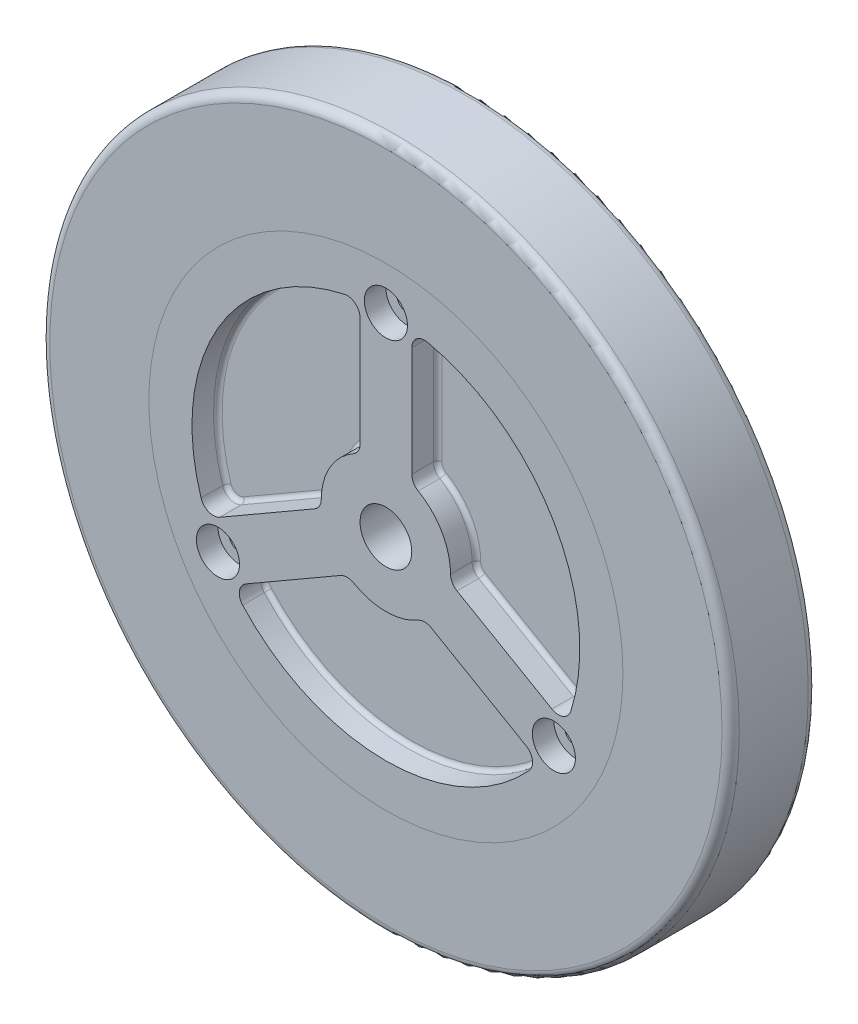
SolidWorks part; units mm, degrees
material "PVC 僵硬"
ref_plane "前视基准面" through (0, 0, 0) normal (0, 0, 1) x (1, 0, 0)
ref_plane "上视基准面" through (0, 0, 0) normal (0, 1, 0) x (1, 0, 0)
ref_plane "右视基准面" through (0, 0, 0) normal (1, 0, 0) x (0, 0, -1)
sketch "草图1" plane through (0, 0, 0) normal (0, 0, 1) x (1, 0, 0)
  circle A0 centre (0, 0) radius 55
  dimension "D1" = 110
extrude "凸台-拉伸1" add sketch "草图1" along normal blind 20
sketch "草图2" plane through (0, 0, 20) normal (0, 0, 1) x (1, 0, 0)
  circle A0 centre (0, 0) radius 2.65
  dimension "D1" = 5.3
extrude "切除-拉伸1" cut sketch "草图2" against normal through all
sketch "草图11" plane through (0, 0, 20) normal (0, 0, 1) x (1, 0, 0)
  circle A0 centre (0, 0) radius 6
  dimension "D1" = 12
extrude "切除-拉伸6" cut sketch "草图11" against normal blind 15
sketch "草图3" plane through (0, 0, 20) normal (0, 0, 1) x (1, 0, 0)
  line L0 (-78.699, 0) -> (94.1302, 0) construction
  line L1 (0, 68.1544) -> (0, -71.9264) construction
  circle A0 centre (0, 45) radius 2.5
  circle A4 centre (38.9711, -22.5) radius 2.5
  circle A5 centre (-38.9711, -22.5) radius 2.5
  circle A6 centre (0, 0) radius 45 construction
  dimension "D1" = 5
  dimension "D2" = 45
  dimension "D3" = 3
extrude "切除-拉伸2" cut sketch "草图3" against normal through all contours A4 | A5 | A0
sketch "草图5" plane through (0, 0, 20) normal (0, 0, 1) x (1, 0, 0)
  circle A0 centre (0, 45) radius 2.5 construction
  circle A2 centre (0, 45) radius 5
  dimension "D1" = 10
extrude "切除-拉伸3" cut sketch "草图5" against normal blind 5
ref_axis "基准轴1" through (0, 0, 0) along (0, 0, 1)
pattern_circular "阵列(圆周)1" count 3 over 360 about axis through (0, 0, 0) along (0, 0, 1) of "切除-拉伸3"
sketch "草图6" plane through (0, 0, 0) normal (0, 0, 1) x (1, 0, 0)
  circle A0 centre (0, 30) radius 2
  circle A1 centre (25.9808, -15) radius 2
  circle A2 centre (-25.9808, -15) radius 2
  dimension "D1" = 4
  dimension "D2" = 30
  dimension "D3" = 3
extrude "切除-拉伸4" cut sketch "草图6" along normal blind 10
sketch "草图7" plane through (0, 0, 0) normal (0, 0, 1) x (1, 0, 0)
  circle A0 centre (0, 0) radius 55 construction
  circle A1 centre (0, 0) radius 55
  circle A2 centre (0, 0) radius 80
  dimension "D1" = 160
extrude "凸台-拉伸2" add sketch "草图7" along normal up to surface (20 mm away) separate body up to face at (-41.4711, -18.1699, 20)
fillet "圆角1" radius 2 2 edges at (80, 0, 0) (80, 0, 20)
ref_plane "基准面1" through (0, 0, 10) normal (0, 0, 1) x (1, 0, 0)
sketch "草图9" plane through (0, 0, 20) normal (0, 0, 1) x (1, 0, 0)
  line L0 (-6, 41.0244) -> (-6, 15.5885)
  line L1 (0, 0) -> (0, 66.1158) construction
  line L2 (6, 41.0244) -> (6, 15.5885)
  line L3 (38.5282, -15.316) -> (16.5, -2.5981)
  line L4 (32.5282, -25.7083) -> (10.5, -12.9904)
  line L5 (-32.5282, -25.7083) -> (-10.5, -12.9904)
  line L6 (-38.5282, -15.316) -> (-16.5, -2.5981)
  arc A0 (-33.2445, -30.3283) -> (33.2445, -30.3283) centre (0, 0) ccw
  arc A1 (-7.5, -12.9904) -> (7.5, -12.9904) centre (0, 0) ccw
  arc A2 (15, 0) -> (7.5, 12.9904) centre (0, 0) ccw
  arc A3 (42.8873, -13.6264) -> (9.6429, 43.9547) centre (0, 0) ccw
  arc A4 (-9.6429, 43.9547) -> (-42.8873, -13.6264) centre (0, 0) ccw
  arc A5 (-7.5, 12.9904) -> (-15, 0) centre (0, 0) ccw
  arc A6 (-10.5, -12.9904) -> (-7.5, -12.9904) centre (-9, -15.5885) cw
  arc A7 (10.5, -12.9904) -> (7.5, -12.9904) centre (9, -15.5885) ccw
  arc A8 (6, 15.5885) -> (7.5, 12.9904) centre (9, 15.5885) ccw
  arc A9 (-6, 15.5885) -> (-7.5, 12.9904) centre (-9, 15.5885) cw
  arc A10 (-16.5, -2.5981) -> (-15, 0) centre (-18, 0) ccw
  arc A11 (-38.5282, -15.316) -> (-42.8873, -13.6264) centre (-40.0282, -12.718) cw
  arc A12 (-32.5282, -25.7083) -> (-33.2445, -30.3283) centre (-31.0282, -28.3064) ccw
  arc A13 (32.5282, -25.7083) -> (33.2445, -30.3283) centre (31.0282, -28.3064) cw
  arc A14 (38.5282, -15.316) -> (42.8873, -13.6264) centre (40.0282, -12.718) ccw
  arc A15 (6, 41.0244) -> (9.6429, 43.9547) centre (9, 41.0244) cw
  arc A16 (-6, 41.0244) -> (-9.6429, 43.9547) centre (-9, 41.0244) ccw
  arc A17 (15, 0) -> (16.5, -2.5981) centre (18, 0) ccw
  point P22 (6, 13.7477)
  point P25 (-6, 13.7477)
  point P38 (6, 44.5982)
  point P41 (-6, 44.5982)
  dimension "D1" = 30
  dimension "D4" = 3
  dimension "D5" = 3
  dimension "D2" = 6
  dimension "D3" = 3
extrude "切除-拉伸5" cut sketch "草图9" against normal blind 6
mirror "镜向1" about plane through (0, 0, 10) normal (0, 0, 1) of "切除-拉伸5"
fillet "圆角2" radius 1 48 edges at (0, -15, 14) (9, -12.5885, 14) (21.5141, -19.3494, 14) (33.9927, -27.8468, 14) (0, -45, 14) (-33.9927, -27.8468, 14) (-21.5141, -19.3494, 14) (-9, -12.5885, 14) (6, 28.3064, 14) (7.1197, 43.362, 14) (38.9711, 22.5, 14) (41.1124, -15.5152, 14) (27.5141, -8.9571, 14) (15.4019, -1.5, 14) (12.9904, 7.5, 14) (6.4019, 14.0885, 14) (-12.9904, 7.5, 14) (-15.4019, -1.5, 14) (-27.5141, -8.9571, 14) (-41.1124, -15.5152, 14) (-38.9711, 22.5, 14) (-7.1197, 43.362, 14) (-6, 28.3064, 14) (-6.4019, 14.0885, 14) (-21.5141, -19.3494, 6) (-33.9927, -27.8468, 6) (0, -45, 6) (33.9927, -27.8468, 6) (21.5141, -19.3494, 6) (9, -12.5885, 6) (0, -15, 6) (-9, -12.5885, 6) (-6, 28.3064, 6) (-7.1197, 43.362, 6) (-38.9711, 22.5, 6) (-41.1124, -15.5152, 6) (-27.5141, -8.9571, 6) (-15.4019, -1.5, 6) (-12.9904, 7.5, 6) (-6.4019, 14.0885, 6) (12.9904, 7.5, 6) (15.4019, -1.5, 6) (27.5141, -8.9571, 6) (41.1124, -15.5152, 6) (38.9711, 22.5, 6) (7.1197, 43.362, 6) (6, 28.3064, 6) (6.4019, 14.0885, 6)
